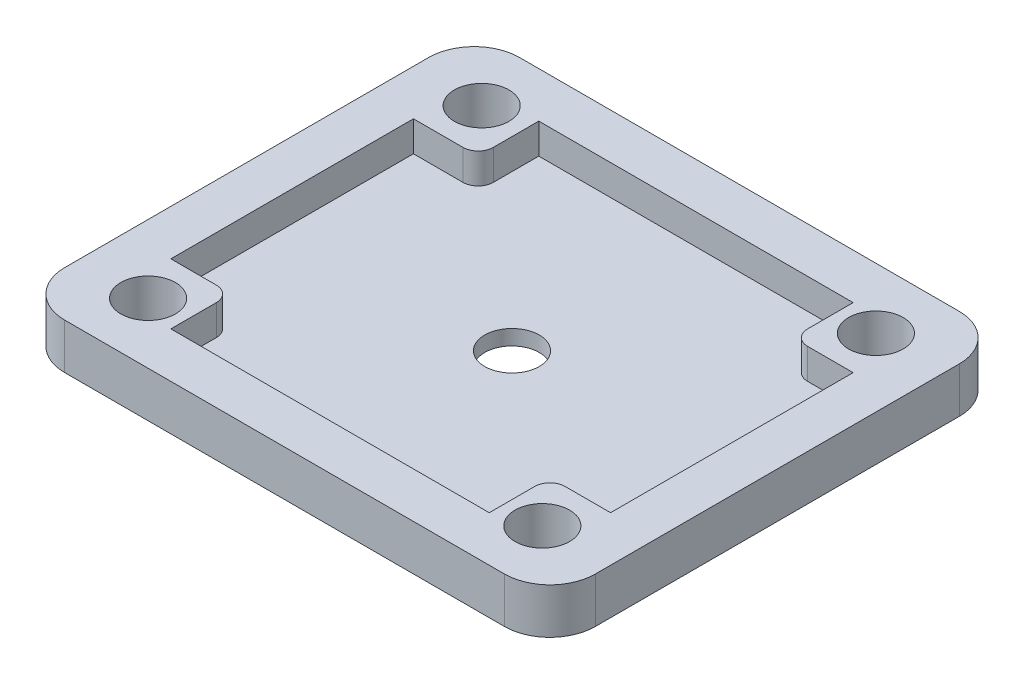
SolidWorks part; units mm, degrees
ref_plane "Front Plane" through (0, 0, 0) normal (0, 0, 1) x (1, 0, 0)
ref_plane "Top Plane" through (0, 0, 0) normal (0, 1, 0) x (1, 0, 0)
ref_plane "Right Plane" through (0, 0, 0) normal (1, 0, 0) x (0, 0, -1)
sketch "Sketch1" plane through (0, 0, 0) normal (0, 1, 0) x (1, 0, 0)
  line L1 (-17.5, -15) -> (17.5, -15)
  line L2 (-17.5, -15) -> (-17.5, 15)
  line L3 (-17.5, 15) -> (17.5, 15)
  line L4 (17.5, -15) -> (17.5, 15)
  line L5 (-17.5, -15) -> (17.5, 15) construction
  line L6 (-17.5, 15) -> (17.5, -15) construction
  point P0 (0, 0)
  dimension "D1" = 30
  dimension "D2" = 35
extrude "Boss-Extrude1" add sketch "Sketch1" along normal blind 3
sketch "Sketch2" plane through (0, 3, 0) normal (0, 1, 0) x (1, 0, 0)
  line L8 (14.5, -12) -> (14.5, 12)
  line L9 (14.5, 12) -> (-14.5, 12)
  line L10 (-14.5, 12) -> (-14.5, -12)
  line L11 (-14.5, -12) -> (14.5, -12)
  line L12 (14.5, -12) -> (14.5, 12)
  line L13 (14.5, 12) -> (-14.5, 12)
  line L14 (-14.5, 12) -> (-14.5, -12)
  line L15 (-14.5, -12) -> (14.5, -12)
  dimension "D1" = 3
extrude "Cut-Extrude1" cut sketch "Sketch2" against normal blind 2
sketch "Sketch5" plane through (0, 1, 0) normal (0, 1, 0) x (1, 0, 0)
  line L1 (-14.5, 12) -> (-10.2337, 12)
  line L2 (-14.5, 12) -> (-14.5, 8)
  line L3 (-14.5, 8) -> (-10.2337, 8)
  line L4 (-10.2337, 12) -> (-10.2337, 8)
  line L5 (14.5, 12) -> (10.5, 12)
  line L6 (14.5, 12) -> (14.5, 8)
  line L7 (14.5, 8) -> (10.5, 8)
  line L8 (10.5, 12) -> (10.5, 8)
  line L9 (14.5, -12) -> (10.5, -12)
  line L10 (14.5, -12) -> (14.5, -8)
  line L11 (14.5, -8) -> (10.5, -8)
  line L12 (10.5, -12) -> (10.5, -8)
  line L13 (-14.5, -12) -> (-10.5, -12)
  line L14 (-14.5, -12) -> (-14.5, -8)
  line L15 (-14.5, -8) -> (-10.5, -8)
  line L16 (-10.5, -12) -> (-10.5, -8)
  dimension "D1" = 4
  dimension "D2" = 4
extrude "Boss-Extrude2" add sketch "Sketch5" along normal blind 2
hole_wizard "M3 Clearance Hole1" positions "Sketch3" profile "Sketch4" hole size "M3" standard "ANSI Metric" end condition through all
sketch "Sketch3" plane through (0, 3, 0) normal (0, 1, 0) x (1, 0, 0)
  line L1 (-13, -11) -> (13, -11)
  line L2 (-13, -11) -> (-13, 11)
  line L3 (-13, 11) -> (13, 11)
  line L4 (13, -11) -> (13, 11)
  line L5 (-13, -11) -> (13, 11) construction
  line L6 (-13, 11) -> (13, -11) construction
  point P1 (0, 0)
  point P2 (13, 11)
  point P73 (-13, -11)
  point P74 (-13, 11)
  point P75 (13, -11)
  point P77 (-16.1694, 10.4212)
  point P78 (0, 0)
  dimension "D1" = 26
  dimension "D2" = 22
sketch "Sketch4" plane through (0, 3, 0) normal (1, 0, 0) x (0, 0, 1)
  line L0 (0, 0) -> (0, 3)
  line L1 (0, 3) -> (1.8, 3)
  line L2 (1.8, 3) -> (1.8, 0)
  line L5 (1.8, 0) -> (0, 0)
  line L11 (0, -6.35) -> (0, 107.95) construction
  dimension "Thru Hole Dia." = 3.6
  dimension "Thru Hole Depth" = 3
fillet "Fillet1" radius 3 4 edges at (17.5, 1.5, 15) (-17.5, 1.5, 15) (-17.5, 1.5, -15) (17.5, 1.5, -15)
fillet "Fillet2" radius 1 4 edges at (-10.5, 2, 8) (10.5, 2, 8) (10.5, 2, -8) (-10.2337, 2, -8)
